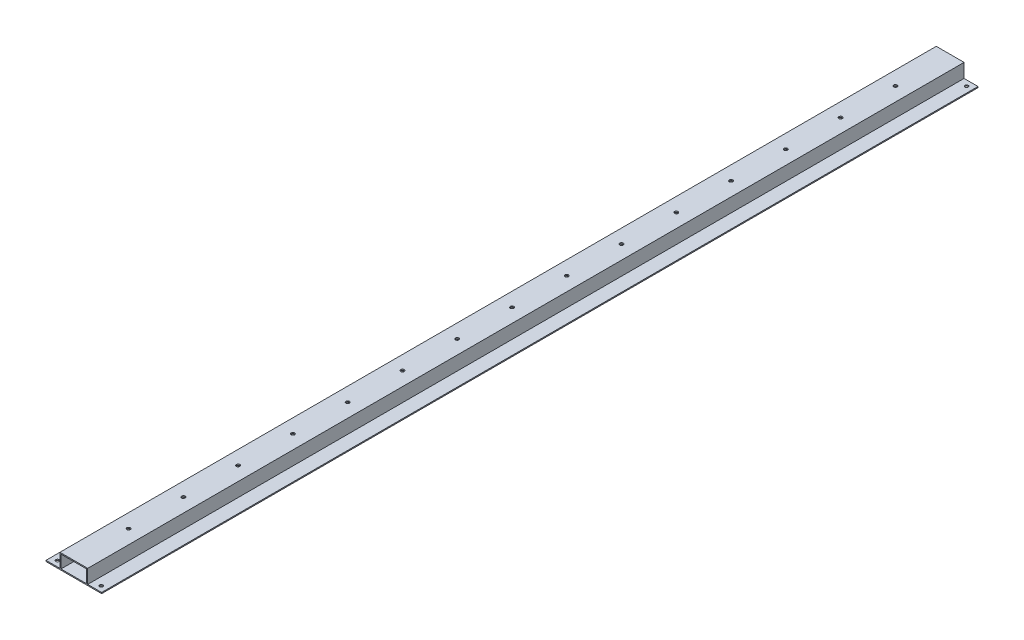
SolidWorks part; units mm, degrees
ref_plane "Alzado" through (0, 0, 0) normal (0, 0, 1) x (1, 0, 0)
ref_plane "Planta" through (0, 0, 0) normal (0, 1, 0) x (1, 0, 0)
ref_plane "Vista lateral" through (0, 0, 0) normal (1, 0, 0) x (0, 0, -1)
sketch "Croquis1" plane through (0, 0, 0) normal (0, 0, 1) x (1, 0, 0)
  line L0 (0, 31.0221) -> (0, -31.113) construction
  line L1 (38.9974, 0) -> (-46.5113, 0) construction
  line L2 (0, 12.7) -> (-11.7, 12.7)
  line L3 (0, 13.7) -> (-12.7, 13.7)
  line L4 (0, 13.7) -> (0, 1) construction
  line L5 (11.7, 1) -> (-11.7, 1)
  line L6 (-12.7, 13.7) -> (-12.7, 1)
  line L7 (25.4, 0) -> (-25.4, 0)
  line L8 (0, 0) -> (0, 1) construction
  line L9 (11.7, 1) -> (-11.7, 1)
  line L10 (-25.4, 0) -> (-25.4, 1)
  line L11 (-11.7, 12.7) -> (-11.7, 1)
  line L12 (-12.7, 1) -> (-25.4, 1)
  line L13 (12.7, 1) -> (25.4, 1)
  line L14 (11.7, 12.7) -> (11.7, 1)
  line L15 (25.4, 0) -> (25.4, 1)
  line L16 (12.7, 13.7) -> (12.7, 1)
  line L17 (0, 13.7) -> (12.7, 13.7)
  line L18 (0, 12.7) -> (11.7, 12.7)
  dimension "D1" = 12.7
  dimension "D2" = 12.7
  dimension "D3" = 1
  dimension "D4" = 1
  dimension "D5" = 25.4
extrude "Saliente-Extruir1" add sketch "Croquis1" along normal mid plane 800 contours L17 L3 L6 L12 L10 L7 L15 L13 L16 L2 L18 L14 L5 L11 region at (6.35, 13.1739, 0)
sketch "Croquis2" plane through (0, 0, 0) normal (0, -1, 0) x (1, 0, 0)
  line L0 (0, 512.6061) -> (0, -444.1411) construction
  line L1 (-90.5126, 0) -> (85.6051, 0) construction
  line L2 (-20, 395) -> (20, 395) construction
  line L3 (-20, 395) -> (-20, -395) construction
  circle A0 centre (-20, 395) radius 1.5
  circle A1 centre (20, 395) radius 1.5
  circle A2 centre (20, -395) radius 1.5
  circle A3 centre (-20, -395) radius 1.5
  dimension "D2" = 3
  dimension "D1" = 20
  dimension "D3" = 395
  dimension "D6" = 90
  dimension "D7" = 40
  dimension "D8" = 790
  dimension "D4" = 2
  dimension "D5" = 2
extrude "Cortar-Extruir1" cut sketch "Croquis2" against normal blind 10
sketch "Croquis3" plane through (0, 0, 0) normal (0, -1, 0) x (1, 0, 0)
  line L0 (0, 409.8961) -> (0, -499.3596) construction
  line L1 (0, 0) -> (0, 50) construction
  line L2 (0, 0) -> (0, -50) construction
  circle A0 centre (0, 0) radius 1.5875
  circle A1 centre (0, 50) radius 1.5875
  circle A2 centre (0, 100) radius 1.5875
  circle A3 centre (0, 150) radius 1.5875
  circle A4 centre (0, 200) radius 1.5875
  circle A5 centre (0, 250) radius 1.5875
  circle A6 centre (0, 300) radius 1.5875
  circle A7 centre (0, 350) radius 1.5875
  circle A8 centre (0, -50) radius 1.5875
  circle A9 centre (0, -100) radius 1.5875
  circle A10 centre (0, -150) radius 1.5875
  circle A11 centre (0, -200) radius 1.5875
  circle A12 centre (0, -250) radius 1.5875
  circle A13 centre (0, -300) radius 1.5875
  circle A14 centre (0, -350) radius 1.5875
  dimension "D1" = 3.175
  dimension "D3" = 50
  dimension "D5" = 50
  dimension "D2" = 8
  dimension "D4" = 8
extrude "Cortar-Extruir2" cut sketch "Croquis3" against normal through all
